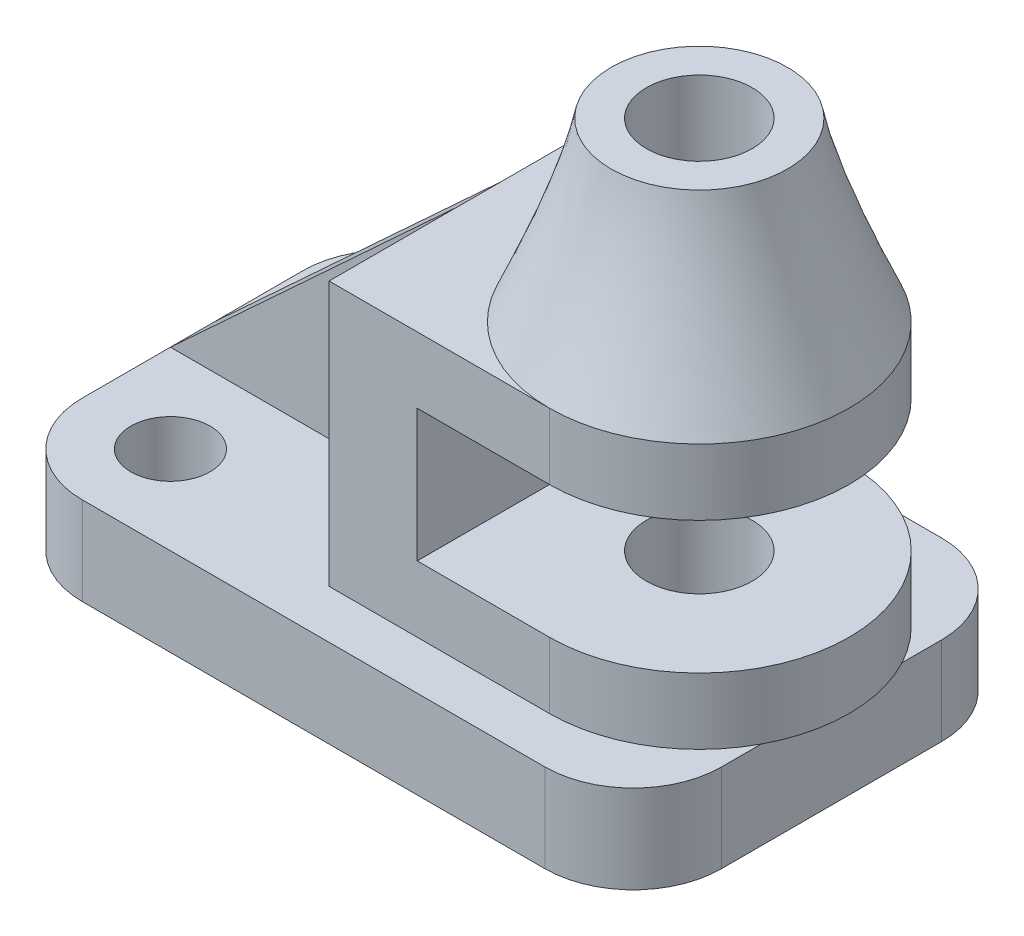
SolidWorks part; units mm, degrees
ref_plane "Front Plane" through (0, 0, 0) normal (0, 0, 1) x (1, 0, 0)
ref_plane "Top Plane" through (0, 0, 0) normal (0, 1, 0) x (1, 0, 0)
ref_plane "Right Plane" through (0, 0, 0) normal (1, 0, 0) x (0, 0, -1)
sketch "Sketch1" plane through (0, 0, 0) normal (0, 1, 0) x (1, 0, 0)
  line L1 (-52.5, 45) -> (52.5, 45)
  line L2 (-72.5, 25) -> (-72.5, -25)
  line L3 (-52.5, -45) -> (52.5, -45)
  line L4 (72.5, 25) -> (72.5, -25)
  line L5 (-72.5, 45) -> (72.5, -45) construction
  line L6 (-72.5, -45) -> (72.5, 45) construction
  arc A0 (52.5, 45) -> (72.5, 25) centre (52.5, 25) cw
  arc A1 (-72.5, -25) -> (-52.5, -45) centre (-52.5, -25) ccw
  arc A2 (-52.5, 45) -> (-72.5, 25) centre (-52.5, 25) ccw
  arc A3 (52.5, -45) -> (72.5, -25) centre (52.5, -25) ccw
  circle A4 centre (-52.5, 25) radius 9
  circle A7 centre (-52.5, -25) radius 9
  point P0 (0, 0)
  dimension "D3" = 20
  dimension "D4" = 18
  dimension "D1" = 145
  dimension "D2" = 90
extrude "Boss-Extrude1" add sketch "Sketch1" against normal blind 20
sketch "Sketch2" plane through (0, 0, 0) normal (0, 1, 0) x (1, 0, 0)
  line L0 (-72.5, 25) -> (-72.5, -25) construction
  line L1 (-7.5, 34) -> (42.5, 34)
  line L2 (-7.5, 34) -> (-7.5, -34)
  line L3 (-7.5, -34) -> (42.5, -34)
  line L5 (-7.5, 34) -> (42.5, -34) construction
  line L6 (-7.5, -34) -> (42.5, 34) construction
  arc A0 (42.5, -34) -> (42.5, 34) centre (42.5, 0) ccw
  point P0 (17.5, 0)
  dimension "D4" = 68
  dimension "D1" = 65
  dimension "D2" = 50
  dimension "D3" = 68
extrude "Boss-Extrude2" add sketch "Sketch2" along normal blind 60
sketch "Sketch3" plane through (0, 60, 0) normal (0, 1, 0) x (1, 0, 0)
  circle A0 centre (42.5, 0) radius 34
ref_plane "Plane1" through (0, 100, 0) normal (0, 1, 0) x (1, 0, 0)
sketch "Sketch6" plane through (0, 100, 0) normal (0, 1, 0) x (1, 0, 0)
  circle A0 centre (42.5, 0) radius 20
  dimension "D1" = 40
loft "Loft1" add profiles "Sketch6", "Sketch3" connector at (22.9899, 100, -4.3996) connector at (10.62, 60, 11.8181)
sketch "Sketch7" plane through (0, 100, 0) normal (0, 1, 0) x (1, 0, 0)
  circle A0 centre (42.5, 0) radius 12
  dimension "D1" = 24
extrude "Cut-Extrude1" cut sketch "Sketch7" against normal through all
sketch "Sketch8" plane through (0, 0, 34) normal (0, 0, 1) x (1, 0, 0)
  line L0 (-7.5, 30) -> (42.5, 30) construction
  line L1 (-7.5, 60) -> (-7.5, 0) construction
  line L2 (42.5, 60) -> (42.5, 0) construction
  line L3 (-7.5, 0) -> (42.5, 0) construction
  line L4 (12.5, 45) -> (115.8142, 45)
  line L5 (12.5, 45) -> (12.5, 15)
  line L6 (12.5, 15) -> (115.8142, 15)
  line L7 (115.8142, 45) -> (115.8142, 15)
  line L8 (12.5, 45) -> (115.8142, 15) construction
  line L9 (12.5, 15) -> (115.8142, 45) construction
  line L10 (-7.5, 60) -> (42.5, 60) construction
  point P6 (64.1571, 30)
  dimension "D1" = 20
  dimension "D2" = 15
  dimension "D3" = 15
extrude "Cut-Extrude2" cut sketch "Sketch8" against normal through all
sketch "Sketch10" plane through (-7.5, 0, 0) normal (-1, 0, 0) x (0, 0, 1)
  line L0 (0, 60) -> (0, 0) construction
  line L1 (-34, 60) -> (34, 60) construction
  line L2 (-34, 0) -> (34, 0) construction
  line L3 (-5, 60) -> (5, 60)
  line L4 (-5, 60) -> (-5, 0)
  line L5 (-5, 0) -> (5, 0)
  line L6 (5, 60) -> (5, 0)
  line L7 (-5, 60) -> (5, 0) construction
  line L8 (-5, 0) -> (5, 60) construction
  point P5 (0, 30)
  dimension "D1" = 10
extrude "Boss-Extrude3" add sketch "Sketch10" along normal through all
sketch "Sketch11" plane through (0, 0, 5) normal (0, 0, 1) x (1, 0, 0)
  line L0 (-72.5, 30) -> (-7.5, 30) construction
  line L1 (-72.5, 0) -> (-72.5, 60) construction
  line L2 (-7.5, 60) -> (-7.5, 0) construction
  line L3 (-7.5, 60) -> (-72.5, 0)
  line L4 (-72.5, 60) -> (-7.5, 60)
  line L5 (-72.5, 60) -> (-72.5, 0)
  line L8 (-72.5, 60) -> (-7.5, 0) construction
  line L9 (-72.5, 0) -> (-7.5, 60) construction
  point P6 (-40, 30)
extrude "Cut-Extrude3" cut sketch "Sketch11" against normal through all
